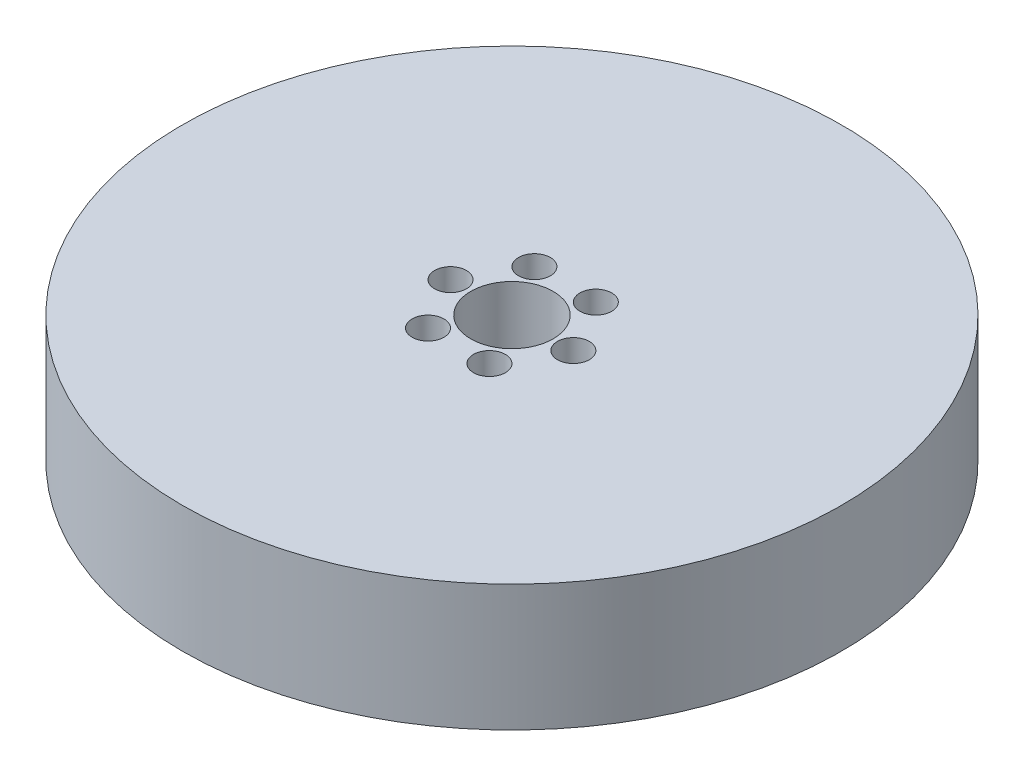
SolidWorks part; units mm, degrees
ref_plane "Front Plane" through (0, 0, 0) normal (0, 0, 1) x (1, 0, 0)
ref_plane "Top Plane" through (0, 0, 0) normal (0, 1, 0) x (1, 0, 0)
ref_plane "Right Plane" through (0, 0, 0) normal (1, 0, 0) x (0, 0, -1)
sketch "Sketch1" plane through (0, 0, 0) normal (0, 1, 0) x (1, 0, 0)
  circle A0 centre (0, 0) radius 60
  dimension "FLANGE_OD" = 120
extrude "Boss-Extrude1" add sketch "Sketch1" along normal blind 23
sketch "Sketch2" plane through (0, 0, 0) normal (0, 1, 0) x (1, 0, 0)
  circle A0 centre (0, 0) radius 7.5
  dimension "BORE_D" = 15
extrude "Cut-Extrude1" cut sketch "Sketch2" along normal through all
sketch "Sketch3" plane through (0, 23, 0) normal (0, 1, 0) x (1, 0, 0)
  circle A0 centre (0, 0) radius 11.1829 construction
  circle A1 centre (-11.1829, 0) radius 2.899
  dimension "BOLT_D" = 5.798
  dimension "BOLT_PCD" = 22.3659
extrude "Cut-Extrude2" cut sketch "Sketch3" against normal blind 17.5932
pattern_circular "CirPattern1" count 6 over 360 about axis through (0, 0, 0) along (0, 1, 0) of "Cut-Extrude2"
